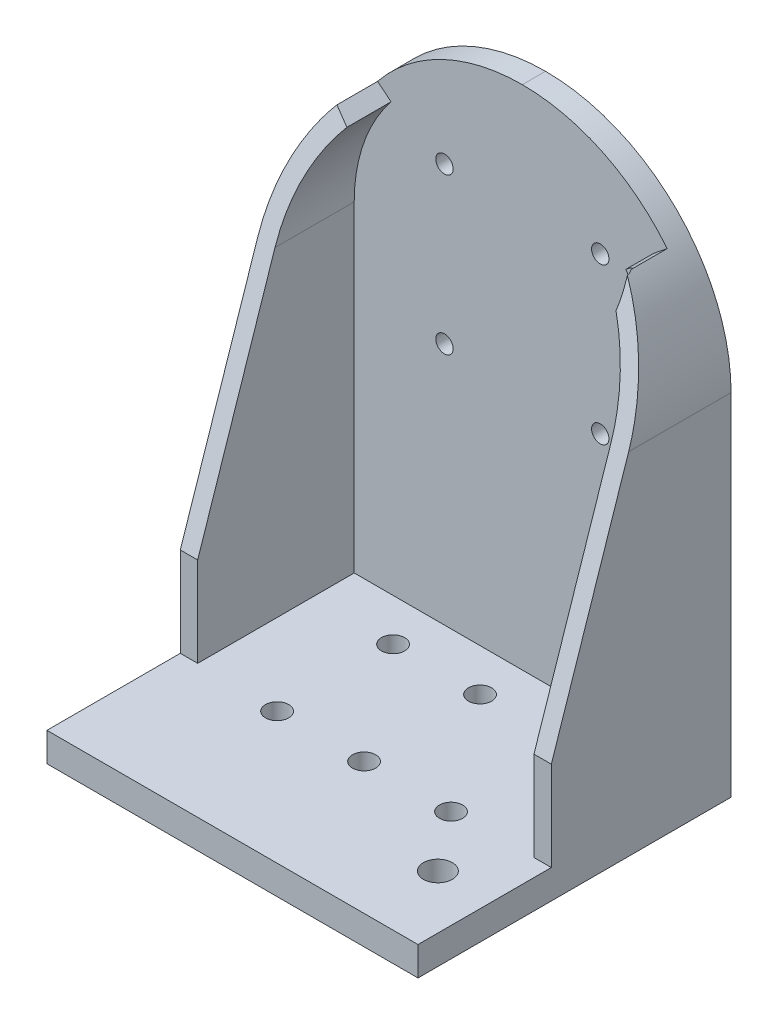
SolidWorks part; units mm, degrees
ref_plane "前视基准面" through (0, 0, 0) normal (0, 0, 1) x (1, 0, 0)
ref_plane "上视基准面" through (0, 0, 0) normal (0, 1, 0) x (1, 0, 0)
ref_plane "右视基准面" through (0, 0, 0) normal (1, 0, 0) x (0, 0, -1)
other "Configuration Table"
sketch "草图2" plane through (0, 0, 0) normal (0, 1, 0) x (1, 0, 0)
  line L1 (-32, 25) -> (32, 25)
  line L2 (-32, 25) -> (-32, -25)
  line L3 (-32, -25) -> (32, -25)
  line L4 (32, 25) -> (32, -25)
  line L5 (-32, 25) -> (32, -25) construction
  line L6 (-32, -25) -> (32, 25) construction
  point P0 (0, 0)
  dimension "D1" = 64
  dimension "D2" = 50
extrude "凸台-拉伸1" add sketch "草图2" along normal blind 5
sketch "草图3" plane through (0, 0, -25) normal (0, 0, -1) x (-1, 0, 0)
  line L1 (-32, 92.44) -> (32, 92.44)
  line L2 (-32, 92.44) -> (-32, 0)
  line L3 (-32, 0) -> (32, 0)
  line L4 (32, 92.44) -> (32, 0)
  line L5 (-32, 92.44) -> (32, 0) construction
  line L6 (-32, 0) -> (32, 92.44) construction
  point P0 (0, 46.22)
  dimension "D1" = 92.44
extrude "凸台-拉伸2" add sketch "草图3" along normal blind 4
sketch "草图4" plane through (0, 0, -29) normal (0, 0, -1) x (-1, 0, 0)
  line L0 (0, 0) -> (0, 60.44) construction
  line L2 (32, 92.44) -> (-32, 92.44) construction
  circle A0 centre (0, 60.44) radius 28.5
  dimension "D1" = 57
  dimension "D2" = 3.5
sketch "草图5" plane through (0, 0, -29) normal (0, 0, -1) x (-1, 0, 0)
  line L0 (-13.435, 73.875) -> (0, 60.44) construction
  circle A0 centre (0, 60.44) radius 19 construction
  circle A1 centre (-13.435, 73.875) radius 1.5
  circle A2 centre (13.435, 73.875) radius 1.5
  circle A3 centre (13.435, 47.005) radius 1.5
  circle A4 centre (-13.435, 47.005) radius 1.5
  dimension "D1" = 38
  dimension "D3" = 3
  dimension "D2" = 45
  dimension "D4" = 4
extrude "切除-拉伸1" cut sketch "草图5" against normal through all
fillet "圆角1" radius 32 2 edges at (-32, 92.44, -27) (32, 92.44, -27)
sketch "草图6" plane through (0, 5, 0) normal (0, 1, 0) x (1, 0, 0)
  line L0 (-15, 17.7) -> (0, 17.7) construction
  line L1 (-32, 25) -> (0, 25) construction
  line L2 (0, 0) -> (0, 17.7) construction
  line L3 (0, 17.7) -> (15, 17.7) construction
  line L4 (-15, -2.3) -> (0, -2.3) construction
  line L5 (0, -2.3) -> (15, -2.3) construction
  circle A0 centre (-15, 17.7) radius 2
  circle A1 centre (15, 17.7) radius 2
  circle A2 centre (0, 17.7) radius 2
  circle A3 centre (-15, -2.3) radius 2
  circle A4 centre (0, -2.3) radius 2
  circle A5 centre (15, -2.3) radius 2
  dimension "D6" = 4
  dimension "D1" = 7.3
  dimension "D2" = 15
  dimension "D3" = 15
  dimension "D5" = 20
  dimension "D4" = 2
extrude "切除-拉伸2" cut sketch "草图6" against normal through all
sketch "草图8" plane through (0, 0, -25) normal (0, 0, 1) x (1, 0, 0)
  line L3 (-32, 60.44) -> (-32, 5)
  line L4 (-32, 5) -> (32, 5)
  line L5 (32, 5) -> (32, 60.44)
  line L6 (-32, 60.44) -> (-32, 5)
  line L8 (32, 5) -> (32, 60.44)
  arc A2 (32, 60.44) -> (0, 92.44) centre (0, 60.44) ccw
  arc A3 (0, 92.44) -> (-32, 60.44) centre (0, 60.44) ccw
  arc A4 (32, 60.44) -> (24.98, 80.44) centre (0, 60.44) ccw
  arc A5 (-24.98, 80.44) -> (-32, 60.44) centre (0, 60.44) ccw
  dimension "D2" = 20
  dimension "D1" = 0
extrude "拉伸-薄壁1" add sketch "草图8" along normal blind 27 thin thin type one direction reverse wall 3
sketch "草图9" plane through (32, 0, 0) normal (1, 0, 0) x (0, 0, -1)
  line L0 (18, 80.44) -> (-2, 20.44)
  line L1 (-2, 80.44) -> (25, 80.44) construction
  line L2 (-2, 5) -> (-2, 60.44) construction
  line L3 (-2, 20.44) -> (-2, 80.44)
  line L4 (-2, 80.44) -> (18, 80.44)
  dimension "D1" = 60
  dimension "D2" = 20
extrude "切除-拉伸3" cut sketch "草图9" against normal through all
sketch "草图10" plane through (0, 0, 0) normal (0, -1, 0) x (1, 0, 0)
  line L1 (32, -29) -> (-32, -29) construction
  line L2 (32, 25) -> (32, -29) construction
  circle A0 centre (22.73, -17.7) radius 2.5
  circle A1 centre (22.73, 12.3) radius 2.5
  dimension "D1" = 5
  dimension "D2" = 11.3
  dimension "D3" = 9.27
  dimension "D4" = 30
extrude "切除-拉伸4" cut sketch "草图10" against normal through all
